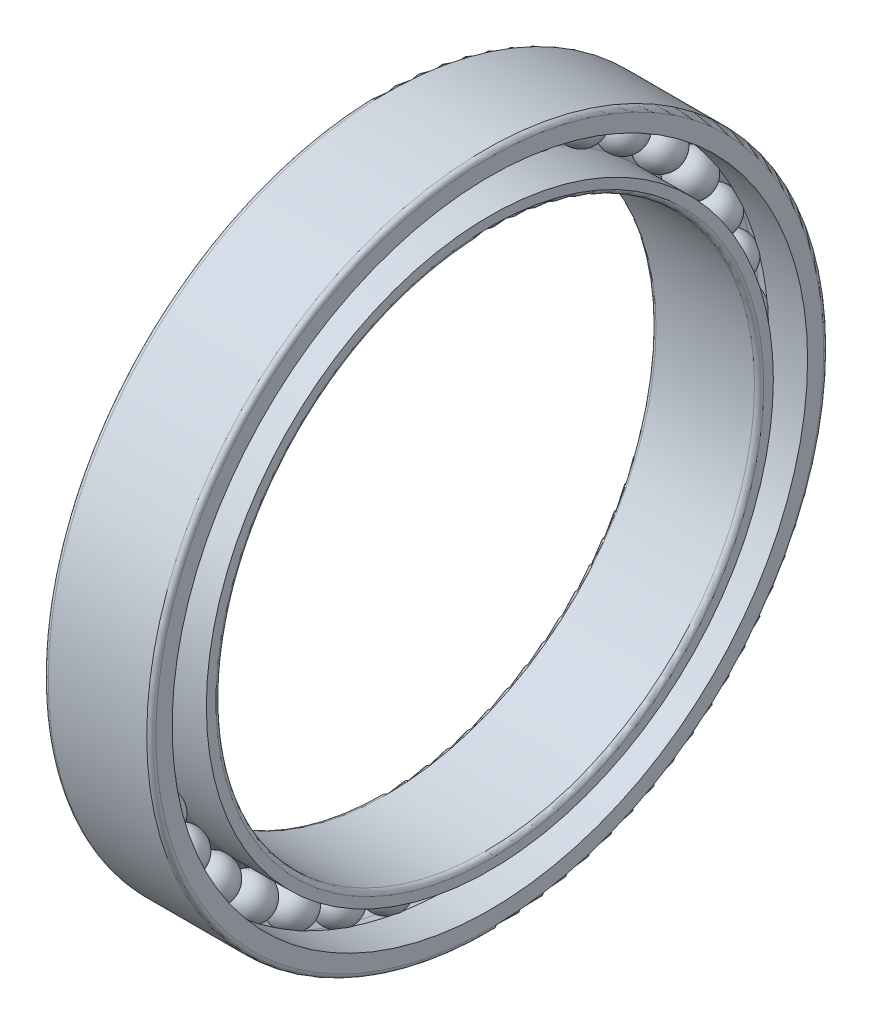
SolidWorks part; units mm, degrees
ref_plane "Plane1" through (0, 0, 0) normal (0, 0, 1) x (1, 0, 0)
ref_plane "Plane2" through (0, 0, 0) normal (0, 1, 0) x (1, 0, 0)
ref_plane "Plane3" through (0, 0, 0) normal (1, 0, 0) x (0, 0, -1)
other "Configuration Table"
sketch "Clipboard" plane through (0, 0, 0) normal (0, 0, 1) x (1, 0, 0)
  line L0 (-10, 0) -> (10, 0) construction
  line L1 (0, 0) -> (17.6205, -13.7666)
  line L2 (0, 0) -> (15.5632, 12.1593)
  line L3 (0, 0) -> (17.6205, -13.7666)
  line L4 (0, 0) -> (-22.3573, -0.3902)
  dimension "BallCLRad" = 19.75
sketch "CagSpiSke" plane through (0, 0, 0) normal (0, 0, 1) x (1, 0, 0)
  line L0 (0.3375, 19.525) -> (0.3375, 19.975)
  line L1 (0.3375, 19.975) -> (-0.3375, 19.975)
  line L2 (-0.3375, 19.975) -> (-0.3375, 19.525)
  line L3 (-0.3375, 19.525) -> (0.3375, 19.525)
  line L4 (-20.6375, 0) -> (20.6375, 0) construction
  line L5 (0, 0) -> (0, 23.7692) construction
  dimension "OD" = 39.95
  dimension "ID" = 39.05
revolve "CageSpine" add sketch "CagSpiSke" angle 0.001 about L4
ref_axis "Axis1" through (-50, 0, 0) along (1, 0, 0)
sketch "CagBalSke" plane through (0, 0, 0) normal (0, 0, 1) x (1, 0, 0)
  line L0 (-1.485, 19.75) -> (1.485, 19.75)
  line L1 (-1.905, 19.75) -> (1.905, 19.75) construction
  line L2 (-10, 0) -> (10, 0) construction
  line L3 (0, 0) -> (0, 24) construction
  arc A0 (1.485, 19.75) -> (-1.485, 19.75) centre (0, 19.75) cw
  dimension "BallCLRad" = 19.75
revolve "CageBall" [suppressed] add sketch "CagBalSke" angle 360 about L1 reverse direction yes
pattern_circular "CageBalls" [suppressed] count 38 every 9.474 about axis through (-50, 0, 0) along (1, 0, 0)
sketch "CagTrmODSke" plane through (0, 0, 0) normal (0, 0, 1) x (1, 0, 0)
  line L0 (1.486, 19.975) -> (1.486, 21.236)
  line L1 (1.486, 21.236) -> (-1.486, 21.236)
  line L2 (-1.486, 21.236) -> (-1.486, 19.975)
  line L3 (-1.486, 19.975) -> (1.486, 19.975)
  line L4 (-20.6375, 0) -> (20.6375, 0) construction
  line L5 (0, 0) -> (0, 25) construction
  dimension "Width" = 2.972
  dimension "ID" = 39.95
  dimension "OD" = 42.472
revolve "CageTrimOD" [suppressed] cut sketch "CagTrmODSke" angle 360 about L4 reverse direction yes
sketch "CagTrmIDSke" plane through (0, 0, 0) normal (0, 0, 1) x (1, 0, 0)
  line L0 (1.486, 18.266) -> (1.486, 19.525)
  line L1 (1.486, 19.525) -> (-1.486, 19.525)
  line L2 (-1.486, 19.525) -> (-1.486, 18.266)
  line L3 (-1.486, 18.266) -> (1.486, 18.266)
  line L4 (-20.6375, 0) -> (20.6375, 0) construction
  line L5 (0, 0) -> (0, 25) construction
  dimension "Width" = 2.972
  dimension "ID" = 36.532
  dimension "OD" = 39.05
revolve "CageTrimID" [suppressed] cut sketch "CagTrmIDSke" angle 360 about L4 reverse direction yes
sketch "BalSimSke" plane through (0, 0, 0) normal (0, 0, 1) x (1, 0, 0)
  line L0 (-10, 0) -> (10, 0) construction
  line L1 (-10, 19.75) -> (10, 19.75) construction
  line L2 (0, 0) -> (0, 23) construction
  circle A0 centre (0, 19.75) radius 1.35
  dimension "BallCLRad" = 19.75
  dimension "Ball_diameter" = 2.7
revolve "BallsSimplified" [suppressed] add sketch "BalSimSke" angle 360 about L0
sketch "BalDetSke" plane through (0, 0, 0) normal (0, 0, 1) x (1, 0, 0)
  line L0 (-1.35, 19.75) -> (1.35, 19.75)
  line L1 (-1.905, 19.75) -> (1.905, 19.75) construction
  line L2 (0, 0) -> (0, 25) construction
  arc A0 (1.35, 19.75) -> (-1.35, 19.75) centre (0, 19.75) cw
  dimension "BallCLRad" = 19.75
  dimension "Ball_diameter" = 2.7
revolve "BallDetailed" add sketch "BalDetSke" angle 360 about L1 reverse direction yes
sketch "InnRacSke" plane through (0, 0, 0) normal (0, 0, 1) x (1, 0, 0)
  line L0 (-0.9724, 18.85) -> (-3.5, 18.85)
  line L1 (-3.5, 18.85) -> (-3.5, 17.8)
  line L2 (-3.2, 17.5) -> (3.2, 17.5)
  line L3 (3.5, 17.8) -> (3.5, 18.425)
  line L4 (0, 18.425) -> (3.5, 18.425)
  line L5 (-20.6375, 0) -> (20.6375, 0) construction
  line L6 (0, 0) -> (0, 30) construction
  arc A0 (-3.5, 17.8) -> (-3.2, 17.5) centre (-3.2, 17.8) ccw
  arc A1 (3.2, 17.5) -> (3.5, 17.8) centre (3.2, 17.8) ccw
  arc A2 (0, 18.425) -> (-0.9724, 18.85) centre (0, 19.75) cw
  dimension "BallCLRad" = 19.75
  dimension "Fillet_radius" = 0.3
  dimension "Ball_diameter" = 2.65
  dimension "ID" = 35
  dimension "OD" = 37.7
  dimension "Width" = 7
revolve "InnerRace" add sketch "InnRacSke" angle 360 about L5 reverse direction yes
sketch "OutRacSke" plane through (0, 0, 0) normal (0, 0, 1) x (1, 0, 0)
  line L0 (0, 21.075) -> (-3.5, 21.075)
  line L1 (-3.5, 21.075) -> (-3.5, 21.7)
  line L2 (-3.2, 22) -> (3.2, 22)
  line L3 (3.5, 21.7) -> (3.5, 20.65)
  line L4 (3.5, 20.65) -> (0.9724, 20.65)
  line L5 (-20.6375, 0) -> (20.6375, 0) construction
  line L6 (0, 0) -> (0, 30) construction
  arc A0 (-3.5, 21.7) -> (-3.2, 22) centre (-3.2, 21.7) cw
  arc A1 (3.2, 22) -> (3.5, 21.7) centre (3.2, 21.7) cw
  arc A2 (0.9724, 20.65) -> (0, 21.075) centre (0, 19.75) ccw
  dimension "BallCLRad" = 19.75
  dimension "Fillet_radius" = 0.3
  dimension "Ball_diameter" = 2.65
  dimension "Width" = 7
revolve "OuterRace" add sketch "OutRacSke" angle 360 about L5 reverse direction yes
pattern_circular "BallsDetailed" count 38 every 9.474 about axis through (-50, 0, 0) along (1, 0, 0) of "BallDetailed"
equation "\"BallCLRad@Clipboard\" = ( \"OD@OutRacSke\" + \"ID@InnRacSke\" ) / 4"
equation "\"BallCLRad@BalSimSke\" = \"BallCLRad@Clipboard\""
equation "\"BallCLRad@BalDetSke\" = \"BallCLRad@Clipboard\""
equation "\"BallCLRad@InnRacSke\" = \"BallCLRad@Clipboard\""
equation "\"BallCLRad@OutRacSke\" = \"BallCLRad@Clipboard\""
equation "\"Ball_diameter@InnRacSke\" = \"Ball_diameter@BalDetSke\" - 0.05"
equation "\"Ball_diameter@OutRacSke\" = \"Ball_diameter@BalDetSke\" - 0.05"
equation "\"Ball_diameter@BalSimSke\" = \"Ball_diameter@BalDetSke\""
equation "\"Width@OutRacSke\" = \"Width@InnRacSke\""
equation "\"Fillet_radius@OutRacSke\" = \"Fillet_radius@InnRacSke\""
equation "\"Max_count@Clipboard\" = int( 3.14159265 / atn(( \"Ball_diameter@BalDetSke\" / 2) / sqr( \"BallCLRad@Clipboard\"  *  \"BallCLRad@Clipboard\" - ( \"Ball_diameter@BalDetSke\" / 2) *  ( \"Ball_diameter@BalDetSke\" / 2))))"
equation "\"Max_count@Clipboard\" = ((sgn( \"Max_count@Clipboard\" - \"Count@Clipboard\" )-1)*( \"Max_count@Clipboard\" - \"Count@Clipboard\" ))/-2+ \"Count@Clipboard\""
equation "\"Count@BallsDetailed\" = int( \"Show_count@Clipboard\" ) "
equation "\"Count@BallsDetailed\" = ((sgn( \"Count@BallsDetailed\" - \"Max_count@Clipboard\" )-1)*( \"Count@BallsDetailed\" - \"Max_count@Clipboard\" ))/-2+ \"Max_count@Clipboard\""
equation "\"Count@BallsDetailed\" = ((sgn( \"Count@BallsDetailed\" - \"Min_count@Clipboard\" )+1)*( \"Count@BallsDetailed\" - \"Min_count@Clipboard\"))/2 +\"Min_count@Clipboard\""
equation "\"Angle@BallsDetailed\" = 360.0 / \"Max_count@Clipboard\""
equation "\"BallCLRad@CagBalSke\" = \"BallCLRad@Clipboard\""
equation "\"Count@CageBalls\" = \"Count@BallsDetailed\""
equation "\"Angle@CageBalls\" = \"Angle@BallsDetailed\""
equation "\"Angle@CageSpine\" =  \"Angle@CageBalls\" * ( \"Count@CageBalls\" -1 + int( \"Count@CageBalls\" / \"Max_count@Clipboard\" ) )  + 0.001 -  int( \"Count@CageBalls\" / \"Max_count@Clipboard\" ) * 0.001"
equation "\"Angle@CageSpine\" =  \"Angle@CageSpine\" * int( \"Min_count@Clipboard\" / 2) + int(1 / \"Min_count@Clipboard\")  * 0.001"
equation "\"CageWallOD@CagBalSke\" =  \"Ball_diameter@BalDetSke\" * 1.1"
equation "\"Thickness@CagSpiSke\" =  \"Ball_diameter@BalDetSke\" * 0.25"
equation "\"OD@CagTrmODSke\" = \"BallCLRad@Clipboard\" * 2 + \"CageWallOD@CagBalSke\" + 0.002"
equation "\"ID@CagTrmODSke\" = \"BallCLRad@Clipboard\" * 2 + \"Ball_diameter@BalDetSke\" / 6"
equation "\"OD@CagTrmIDSke\" = \"BallCLRad@Clipboard\" * 2 - \"Ball_diameter@BalDetSke\" / 6"
equation "\"ID@CagTrmIDSke\" = \"BallCLRad@Clipboard\" * 2 - \"CageWallOD@CagBalSke\" + 0.002"
equation "\"OD@CagSpiSke\" = \"ID@CagTrmODSke\""
equation "\"ID@CagSpiSke\" = \"OD@CagTrmIDSke\""
equation "\"Width@CagTrmODSke\" = \"CageWallOD@CagBalSke\" + 0.002"
equation "\"Width@CagTrmIDSke\" = \"CageWallOD@CagBalSke\" + 0.002"
